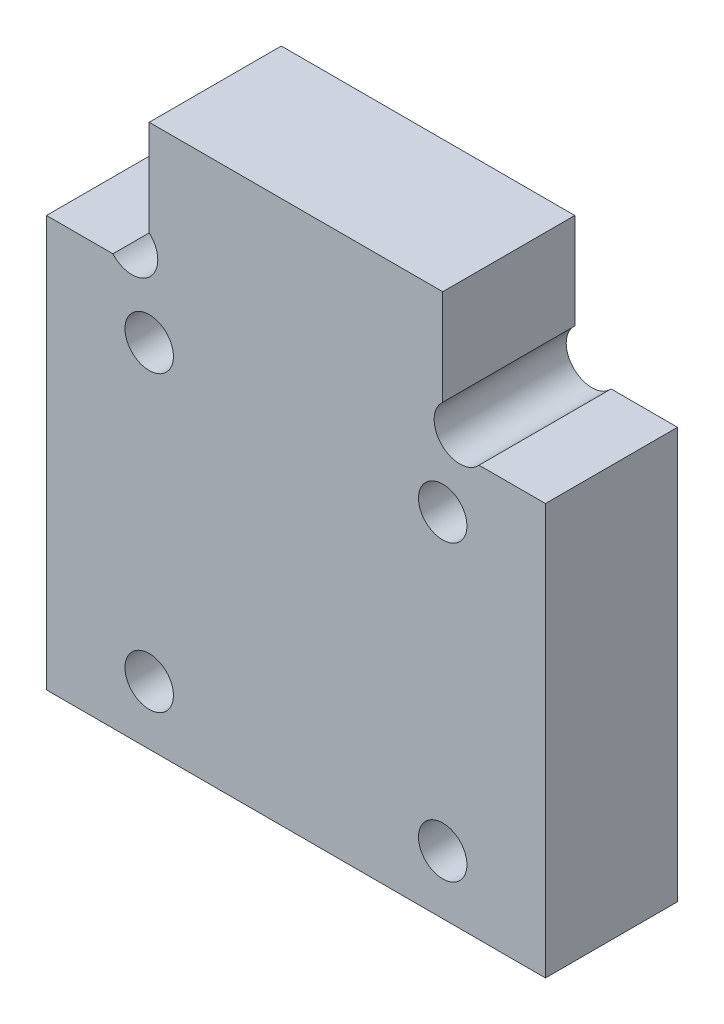
SolidWorks part; units mm, degrees
ref_plane "Plan de face" through (0, 0, 0) normal (0, 0, 1) x (1, 0, 0)
ref_plane "Plan de dessus" through (0, 0, 0) normal (0, 1, 0) x (1, 0, 0)
ref_plane "Plan de droite" through (0, 0, 0) normal (1, 0, 0) x (0, 0, -1)
sketch "Esquisse1" plane through (0, 0, 0) normal (0, 0, 1) x (1, 0, 0)
  line L1 (0, 0) -> (34, 0)
  line L2 (0, 0) -> (0, 28)
  line L3 (0, 28) -> (34, 28)
  line L4 (34, 0) -> (34, 28)
  dimension "D1" = 28
  dimension "D2" = 34
extrude "Boss.-Extru.1" add sketch "Esquisse1" along normal blind 9
sketch "Esquisse2" plane through (0, 0, 9) normal (0, 0, 1) x (1, 0, 0)
  line L0 (17, 28) -> (17, 37) construction
  line L1 (34, 28) -> (0, 28) construction
  line L2 (27, 37) -> (7, 37)
  line L3 (7, 37) -> (7, 28)
  line L4 (7, 28) -> (27, 28)
  line L5 (27, 37) -> (27, 28)
  dimension "D1" = 20
  dimension "D2" = 9
extrude "Boss.-Extru.2" add sketch "Esquisse2" against normal up to vertex (9 mm away) up to point (0, 28, 0)
sketch "Esquisse3" plane through (0, 0, 9) normal (0, 0, 1) x (1, 0, 0)
  line L0 (7, 28) -> (0, 28) construction
  line L1 (7, 37) -> (7, 28) construction
  line L2 (4.5251, 28) -> (7, 30.4749)
  line L3 (5.8314, 29.1686) -> (5.7626, 29.2374) construction
  line L4 (7, 28) -> (7.0707, 27.9293) construction
  line L5 (17, 37) -> (17, 32.4749) construction
  line L6 (27, 37) -> (7, 37) construction
  line L7 (27, 28) -> (26.9293, 27.9293) construction
  line L8 (28.1686, 29.1686) -> (28.2374, 29.2374) construction
  line L9 (29.4749, 28) -> (27, 30.4749)
  arc A0 (4.5251, 28) -> (7, 30.4749) centre (5.8314, 29.1686) ccw
  arc A1 (29.4749, 28) -> (27, 30.4749) centre (28.1686, 29.1686) cw
  dimension "D1" = 3.5
  dimension "D2" = 0.1
extrude "Enlèv. mat.-Extru.1" cut sketch "Esquisse3" against normal through all both and the other way through all
sketch "Esquisse4" plane through (0, 0, 9) normal (0, 0, 1) x (1, 0, 0)
  line L0 (0, 14) -> (34, 14) construction
  line L1 (0, 28) -> (0, 0) construction
  line L2 (34, 0) -> (34, 28) construction
  line L3 (17, 14) -> (17, 21.7109) construction
  line L4 (0, 0) -> (34, 0) construction
  circle A0 centre (7, 24) radius 1.65
  circle A1 centre (27, 24) radius 1.65
  circle A2 centre (27, 4) radius 1.65
  circle A3 centre (7, 4) radius 1.65
  dimension "D1" = 20
  dimension "D2" = 3.3
  dimension "D3" = 20
  dimension "D4" = 14
extrude "Enlèv. mat.-Extru.2" cut sketch "Esquisse4" against normal through all both and the other way through all
